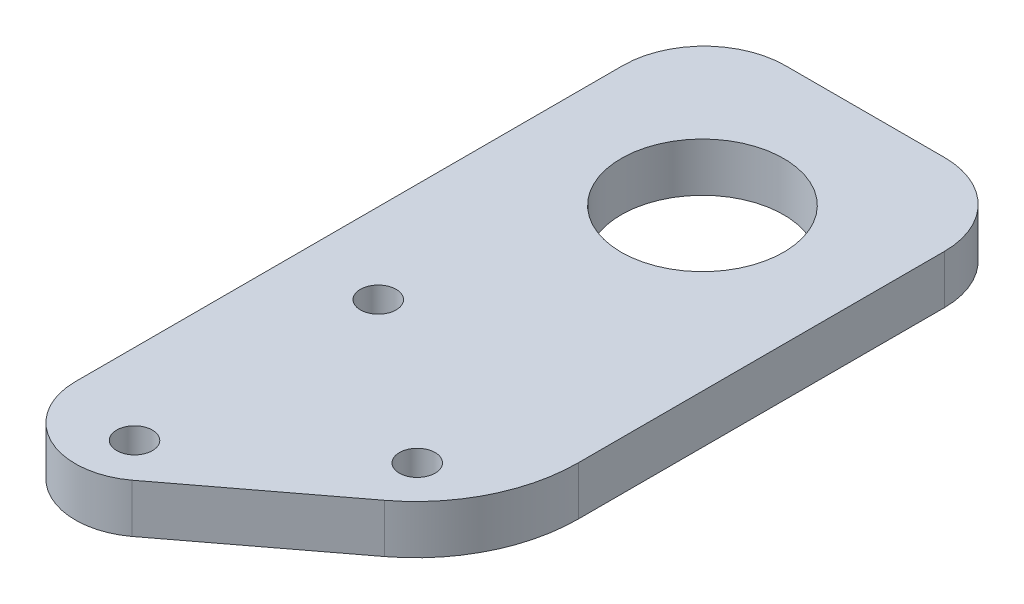
SolidWorks part; units mm, degrees
ref_plane "Front Plane" through (0, 0, 0) normal (0, 0, 1) x (1, 0, 0)
ref_plane "Top Plane" through (0, 0, 0) normal (0, 1, 0) x (1, 0, 0)
ref_plane "Right Plane" through (0, 0, 0) normal (1, 0, 0) x (0, 0, -1)
sketch "Sketch1" plane through (0, 0, 0) normal (0, 1, 0) x (1, 0, 0)
  line L5 (-9.9, 27.5) -> (-9.9, -6.1922)
  line L6 (-2.906, -9.7015) -> (5.9386, -3.0011)
  line L19 (9.9, 27.5) -> (9.9, 4.9698)
  line L20 (4.9, 32.5) -> (-4.9, 32.5)
  circle A0 centre (-4.95, 7.5) radius 1.1
  circle A1 centre (-4.95, -7.5) radius 1.1
  circle A2 centre (4.95, 0) radius 1.1
  arc A3 (-9.9, -6.1922) -> (-2.906, -9.7015) centre (-5.5226, -6.1922) ccw
  arc A5 (9.9, 4.9698) -> (5.9386, -3.0011) centre (-0.1, 4.9698) cw
  circle A6 centre (0, 22.5) radius 5
  arc A7 (-9.9, 27.5) -> (-4.9, 32.5) centre (-4.9, 27.5) cw
  arc A8 (9.9, 27.5) -> (4.9, 32.5) centre (4.9, 27.5) ccw
  point P0 (0, 0)
  point P2 (-9.9, -6.1922)
  point P23 (8.2713, -1.2339)
  dimension "D1" = 2.2
  dimension "D2" = 2.2
  dimension "D3" = 2.2
  dimension "D4" = 10
  dimension "D5" = 10
  dimension "D6" = 5
  dimension "D7" = 5
extrude "Boss-Extrude1" add sketch "Sketch1" along normal blind 3
